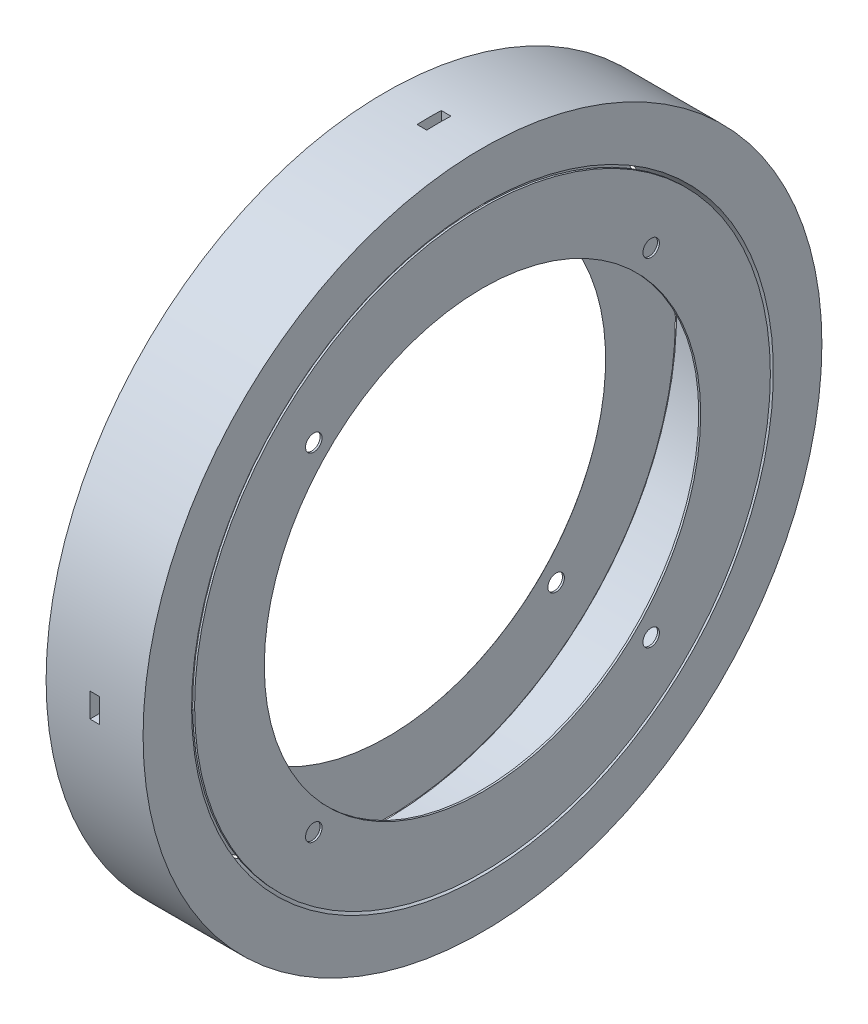
SolidWorks part; units mm, degrees
ref_plane "前视基准面" through (0, 0, 0) normal (0, 0, 1) x (1, 0, 0)
ref_plane "上视基准面" through (0, 0, 0) normal (0, 1, 0) x (1, 0, 0)
ref_plane "右视基准面" through (0, 0, 0) normal (1, 0, 0) x (0, 0, -1)
sketch "草图1" plane through (0, 0, 0) normal (0, 0, 1) x (1, 0, 0)
  line L0 (0, 35) -> (0, 0)
  line L1 (0, 0) -> (10, 0)
  line L2 (10, 0) -> (10, 35)
  line L3 (10, 35) -> (0, 35)
  line L4 (0, 0) -> (10, 0) construction
revolve "旋转1" add sketch "草图1" angle 360 about L4
hole_wizard "M52 间隙孔1" positions "草图3" profile "草图2" hole size "M52" standard "ANSI Metric"
sketch "草图3" plane through (0, 0, 0) normal (-1, 0, 0) x (0, 0, 1)
  point P0 (0, 0)
sketch "草图2" plane through (0, 0, 0) normal (0, 1, 0) x (0, 0, 1)
  line L0 (0, 0) -> (0, 10)
  line L1 (0, 10) -> (30, 10)
  line L2 (30, 10) -> (30, 0)
  line L5 (30, 0) -> (0, 0)
  line L11 (0, -6.35) -> (0, 107.95) construction
  dimension "通孔孔直径" = 60
  dimension "通孔孔深度" = 10
ref_plane "基准面4" through (0.2, 0, 0) normal (1, 0, 0) x (0, 0, -1)
sketch "草图4" plane through (0.2, 0, 0) normal (1, 0, 0) x (0, 0, -1)
  circle A0 centre (0, 0) radius 29.6875
extrude "凸台-拉伸1" add sketch "草图4" against normal blind 0.2
ref_plane "基准面5" through (9.8, 0, 0) normal (-1, 0, 0) x (0, -1, 0)
sketch "草图6" plane through (9.8, 0, 0) normal (-1, 0, 0) x (0, -1, 0)
  circle A0 centre (0, 0) radius 29.6875
extrude "凸台-拉伸2" add sketch "草图6" against normal blind 0.2
sketch "草图7" plane through (0, 0, 0) normal (-1, 0, 0) x (0, 0, 1)
  circle A0 centre (0, 0) radius 22.5
extrude "切除-拉伸1" cut sketch "草图7" against normal blind 3.3333
ref_plane "基准面6" through (3.3333, 0, 0) normal (-1, 0, 0) x (0, -1, 0)
sketch "草图8" plane through (3.3333, 0, 0) normal (-1, 0, 0) x (0, -1, 0)
  circle A0 centre (0, 0) radius 22.5
ref_plane "基准面7" through (5, 0, 0) normal (-1, 0, 0) x (0, -1, 0)
sketch "草图9" plane through (5, 0, 0) normal (-1, 0, 0) x (0, -1, 0)
  circle A0 centre (0, 0) radius 23.1
sketch "草图10" plane through (10, 0, 0) normal (1, 0, 0) x (0, 0, -1)
  circle A0 centre (0, 0) radius 22.5
extrude "切除-拉伸4" cut sketch "草图10" against normal blind 3.3333
ref_plane "基准面8" through (0, 0, 26.6667) normal (0, 0, 1) x (1, 0, 0)
sketch "草图11" plane through (0, 0, 26.6667) normal (0, 0, 1) x (1, 0, 0)
  line L0 (5.5, 1.25) -> (4.5, 1.25)
  line L1 (4.5, 1.25) -> (4.5, -1.25)
  line L2 (4.5, -1.25) -> (5.5, -1.25)
  line L3 (5.5, -1.25) -> (5.5, 1.25)
extrude "切除-拉伸5" cut sketch "草图11" against normal up to next
ref_plane "基准面9" through (0, 0, -26.6667) normal (0, 0, -1) x (-1, 0, 0)
sketch "草图12" plane through (0, 0, -26.6667) normal (0, 0, -1) x (-1, 0, 0)
  line L0 (-4.5, 1.25) -> (-5.5, 1.25)
  line L1 (-5.5, 1.25) -> (-5.5, -1.25)
  line L2 (-5.5, -1.25) -> (-4.5, -1.25)
  line L3 (-4.5, -1.25) -> (-4.5, 1.25)
extrude "切除-拉伸6" cut sketch "草图12" against normal up to next
ref_plane "基准面10" through (0, -26.6667, 0) normal (0, -1, 0) x (1, 0, 0)
sketch "草图13" plane through (0, -26.6667, 0) normal (0, -1, 0) x (1, 0, 0)
  line L0 (4.5, -1.25) -> (5.5, -1.25)
  line L1 (5.5, -1.25) -> (5.5, 1.25)
  line L2 (5.5, 1.25) -> (4.5, 1.25)
  line L3 (4.5, 1.25) -> (4.5, -1.25)
extrude "切除-拉伸7" cut sketch "草图13" against normal up to next
ref_plane "基准面11" through (0, 26.6667, 0) normal (0, 1, 0) x (1, 0, 0)
sketch "草图14" plane through (0, 26.6667, 0) normal (0, 1, 0) x (1, 0, 0)
  line L0 (5.5, 1.25) -> (4.5, 1.25)
  line L1 (4.5, 1.25) -> (4.5, -1.25)
  line L2 (4.5, -1.25) -> (5.5, -1.25)
  line L3 (5.5, -1.25) -> (5.5, 1.25)
extrude "切除-拉伸8" cut sketch "草图14" against normal up to next
hole_wizard "Ø1.7 (1.7) 直径孔1" positions "草图16" profile "草图15" hole size "Ø1.7" standard "ANSI Metric"
sketch "草图16" plane through (10, 0, 0) normal (1, 0, 0) x (0, 0, -1)
  point P0 (-17.3948, 17.3948)
  point P1 (-17.3948, -17.3948)
  point P2 (17.3948, -17.3948)
  point P3 (17.3948, 17.3948)
sketch "草图15" plane through (10, 17.3948, 17.3948) normal (0, 1, 0) x (0, 0, -1)
  line L0 (0, 0) -> (0, 0.85)
  line L1 (0, 0.85) -> (0.85, 0.85)
  line L2 (0.85, 0.85) -> (0.85, 0)
  line L5 (0.85, 0) -> (0, 0)
  line L10 (0, 0.85) -> (-0.85, 0.85) construction
  line L11 (0, -6.35) -> (0, 107.95) construction
  dimension "孔直径" = 1.7
  dimension "孔深度" = 0.85
  dimension "导头角度" = 180
hole_wizard "Ø1.7 (1.7) 直径孔2" positions "草图18" profile "草图17" hole size "Ø1.7" standard "ANSI Metric"
sketch "草图18" plane through (0, 0, 0) normal (-1, 0, 0) x (0, 0, 1)
  point P0 (17.3948, 17.3948)
  point P1 (17.3948, -17.3948)
  point P2 (-17.3948, -17.3948)
  point P3 (-17.3948, 17.3948)
  dimension "D1" = 24.6
sketch "草图17" plane through (0, 17.3948, 17.3948) normal (0, 1, 0) x (0, 0, 1)
  line L0 (0, 0) -> (0, 0.85)
  line L1 (0, 0.85) -> (0.85, 0.85)
  line L2 (0.85, 0.85) -> (0.85, 0)
  line L5 (0.85, 0) -> (0, 0)
  line L10 (0, 0.85) -> (-0.85, 0.85) construction
  line L11 (0, -6.35) -> (0, 107.95) construction
  dimension "孔直径" = 1.7
  dimension "孔深度" = 0.85
  dimension "导头角度" = 180
fillet "圆角2" radius 0.6 1 edges at (0, 0, -22.5)
